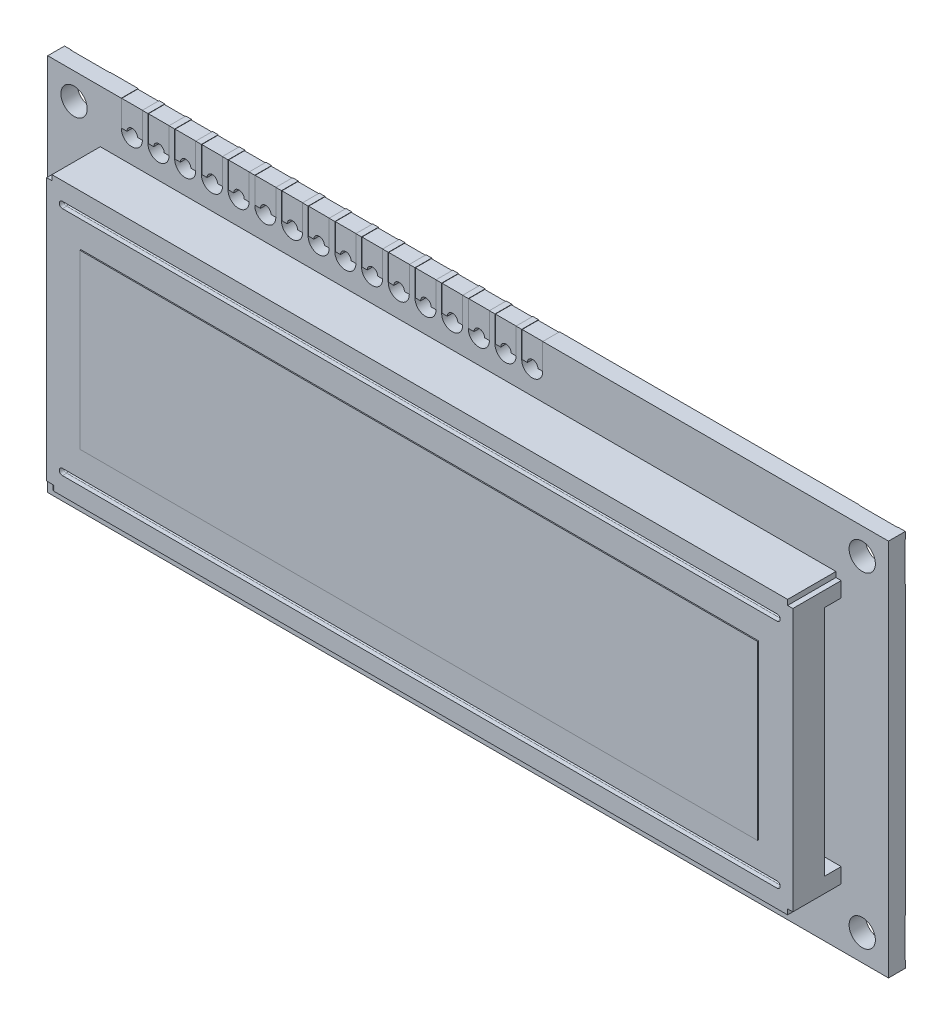
SolidWorks part; units mm, degrees
ref_plane "Front Plane" through (0, 0, 0) normal (0, 0, 1) x (1, 0, 0)
ref_plane "Top Plane" through (0, 0, 0) normal (0, 1, 0) x (1, 0, 0)
ref_plane "Right Plane" through (0, 0, 0) normal (1, 0, 0) x (0, 0, -1)
ref_plane "Plane1" through (0, 0, 6.2) normal (0, 0, 1) x (1, 0, 0)
sketch "Sketch1" plane through (0, 0, 6.2) normal (0, 0, 1) x (1, 0, 0)
  line L0 (-35, 13) -> (-35, -13)
  line L1 (-35, -13) -> (35, -13)
  line L2 (35, -13) -> (35, 13)
  line L3 (35, 13) -> (-35, 13)
extrude "Boss-Extrude1" add sketch "Sketch1" against normal blind 4.6
sketch "Sketch2" plane through (-35, 0, 0) normal (-1, 0, 0) x (0, 0, 1)
  line L0 (1.6, -12.5) -> (1.6, 12.5)
  line L1 (1.6, 12.5) -> (6.2, 12.5)
  line L2 (6.2, 12.5) -> (6.2, -12.5)
  line L3 (6.2, -12.5) -> (1.6, -12.5)
extrude "Boss-Extrude2" add sketch "Sketch2" along normal blind 0.5
sketch "Sketch3" plane through (35, 0, 0) normal (1, 0, 0) x (0, 0, -1)
  line L0 (-1.6, 12.5) -> (-1.6, -12.5)
  line L1 (-1.6, -12.5) -> (-6.2, -12.5)
  line L2 (-6.2, -12.5) -> (-6.2, 12.5)
  line L3 (-6.2, 12.5) -> (-1.6, 12.5)
extrude "Boss-Extrude3" add sketch "Sketch3" along normal blind 0.5
ref_plane "Plane2" through (0, 11.0678, 0) normal (0, 1, 0) x (1, 0, 0)
sketch "Sketch4" plane through (0, 11.0678, 0) normal (0, 1, 0) x (1, 0, 0)
  line L0 (-35.5, -3.2) -> (35.5, -3.2)
  line L1 (35.5, -3.2) -> (35.5, -1.6)
  line L2 (35.5, -1.6) -> (-35.5, -1.6)
  line L3 (-35.5, -1.6) -> (-35.5, -3.2)
extrude "Cut-Extrude1" cut sketch "Sketch4" against normal blind 22.1357
ref_plane "Plane3" through (0, 0, 1.6) normal (0, 0, 1) x (1, 0, 0)
sketch "Sketch5" plane through (0, 0, 1.6) normal (0, 0, 1) x (1, 0, 0)
  line L0 (-40, 18) -> (-40, -18)
  line L1 (-40, -18) -> (40, -18)
  line L2 (40, -18) -> (40, 18)
  line L3 (40, 18) -> (-40, 18)
extrude "Boss-Extrude4" add sketch "Sketch5" against normal blind 1.6
sketch "Sketch6" plane through (0, 0, 1.6) normal (0, 0, 1) x (1, 0, 0)
  line L0 (-31, 18) -> (-33, 18)
  line L1 (-33, 18) -> (-33, 15.5)
  line L2 (-31, 15.5) -> (-31, 18)
  arc A0 (-33, 15.5) -> (-31, 15.5) centre (-32, 15.5) ccw
extrude "Cut-Extrude2" cut sketch "Sketch6" against normal through all
sketch "Sketch7" plane through (0, 0, 1.6) normal (0, 0, 1) x (1, 0, 0)
  line L0 (-28.46, 18) -> (-30.46, 18)
  line L1 (-30.46, 18) -> (-30.46, 15.5)
  line L2 (-28.46, 15.5) -> (-28.46, 18)
  arc A0 (-30.46, 15.5) -> (-28.46, 15.5) centre (-29.46, 15.5) ccw
extrude "Cut-Extrude3" cut sketch "Sketch7" against normal through all
sketch "Sketch8" plane through (0, 0, 1.6) normal (0, 0, 1) x (1, 0, 0)
  line L0 (-25.92, 18) -> (-27.92, 18)
  line L1 (-27.92, 18) -> (-27.92, 15.5)
  line L2 (-25.92, 15.5) -> (-25.92, 18)
  arc A0 (-27.92, 15.5) -> (-25.92, 15.5) centre (-26.92, 15.5) ccw
extrude "Cut-Extrude4" cut sketch "Sketch8" against normal through all
sketch "Sketch9" plane through (0, 0, 1.6) normal (0, 0, 1) x (1, 0, 0)
  line L0 (-23.38, 18) -> (-25.38, 18)
  line L1 (-25.38, 18) -> (-25.38, 15.5)
  line L2 (-23.38, 15.5) -> (-23.38, 18)
  arc A0 (-25.38, 15.5) -> (-23.38, 15.5) centre (-24.38, 15.5) ccw
extrude "Cut-Extrude5" cut sketch "Sketch9" against normal through all
sketch "Sketch10" plane through (0, 0, 1.6) normal (0, 0, 1) x (1, 0, 0)
  line L0 (-20.84, 18) -> (-22.84, 18)
  line L1 (-22.84, 18) -> (-22.84, 15.5)
  line L2 (-20.84, 15.5) -> (-20.84, 18)
  arc A0 (-22.84, 15.5) -> (-20.84, 15.5) centre (-21.84, 15.5) ccw
extrude "Cut-Extrude6" cut sketch "Sketch10" against normal through all
sketch "Sketch11" plane through (0, 0, 1.6) normal (0, 0, 1) x (1, 0, 0)
  line L0 (-18.3, 18) -> (-20.3, 18)
  line L1 (-20.3, 18) -> (-20.3, 15.5)
  line L2 (-18.3, 15.5) -> (-18.3, 18)
  arc A0 (-20.3, 15.5) -> (-18.3, 15.5) centre (-19.3, 15.5) ccw
extrude "Cut-Extrude7" cut sketch "Sketch11" against normal through all
sketch "Sketch12" plane through (0, 0, 1.6) normal (0, 0, 1) x (1, 0, 0)
  line L0 (-15.76, 18) -> (-17.76, 18)
  line L1 (-17.76, 18) -> (-17.76, 15.5)
  line L2 (-15.76, 15.5) -> (-15.76, 18)
  arc A0 (-17.76, 15.5) -> (-15.76, 15.5) centre (-16.76, 15.5) ccw
extrude "Cut-Extrude8" cut sketch "Sketch12" against normal through all
sketch "Sketch13" plane through (0, 0, 1.6) normal (0, 0, 1) x (1, 0, 0)
  line L0 (-13.22, 18) -> (-15.22, 18)
  line L1 (-15.22, 18) -> (-15.22, 15.5)
  line L2 (-13.22, 15.5) -> (-13.22, 18)
  arc A0 (-15.22, 15.5) -> (-13.22, 15.5) centre (-14.22, 15.5) ccw
extrude "Cut-Extrude9" cut sketch "Sketch13" against normal through all
sketch "Sketch14" plane through (0, 0, 1.6) normal (0, 0, 1) x (1, 0, 0)
  line L0 (-10.68, 18) -> (-12.68, 18)
  line L1 (-12.68, 18) -> (-12.68, 15.5)
  line L2 (-10.68, 15.5) -> (-10.68, 18)
  arc A0 (-12.68, 15.5) -> (-10.68, 15.5) centre (-11.68, 15.5) ccw
extrude "Cut-Extrude10" cut sketch "Sketch14" against normal through all
sketch "Sketch15" plane through (0, 0, 1.6) normal (0, 0, 1) x (1, 0, 0)
  line L0 (-8.14, 18) -> (-10.14, 18)
  line L1 (-10.14, 18) -> (-10.14, 15.5)
  line L2 (-8.14, 15.5) -> (-8.14, 18)
  arc A0 (-10.14, 15.5) -> (-8.14, 15.5) centre (-9.14, 15.5) ccw
extrude "Cut-Extrude11" cut sketch "Sketch15" against normal through all
sketch "Sketch16" plane through (0, 0, 1.6) normal (0, 0, 1) x (1, 0, 0)
  line L0 (-5.6, 18) -> (-7.6, 18)
  line L1 (-7.6, 18) -> (-7.6, 15.5)
  line L2 (-5.6, 15.5) -> (-5.6, 18)
  arc A0 (-7.6, 15.5) -> (-5.6, 15.5) centre (-6.6, 15.5) ccw
extrude "Cut-Extrude12" cut sketch "Sketch16" against normal through all
sketch "Sketch17" plane through (0, 0, 1.6) normal (0, 0, 1) x (1, 0, 0)
  line L0 (-3.06, 18) -> (-5.06, 18)
  line L1 (-5.06, 18) -> (-5.06, 15.5)
  line L2 (-3.06, 15.5) -> (-3.06, 18)
  arc A0 (-5.06, 15.5) -> (-3.06, 15.5) centre (-4.06, 15.5) ccw
extrude "Cut-Extrude13" cut sketch "Sketch17" against normal through all
sketch "Sketch18" plane through (0, 0, 1.6) normal (0, 0, 1) x (1, 0, 0)
  line L0 (-0.52, 18) -> (-2.52, 18)
  line L1 (-2.52, 18) -> (-2.52, 15.5)
  line L2 (-0.52, 15.5) -> (-0.52, 18)
  arc A0 (-2.52, 15.5) -> (-0.52, 15.5) centre (-1.52, 15.5) ccw
extrude "Cut-Extrude14" cut sketch "Sketch18" against normal through all
sketch "Sketch19" plane through (0, 0, 1.6) normal (0, 0, 1) x (1, 0, 0)
  line L0 (2.02, 18) -> (0.02, 18)
  line L1 (0.02, 18) -> (0.02, 15.5)
  line L2 (2.02, 15.5) -> (2.02, 18)
  arc A0 (0.02, 15.5) -> (2.02, 15.5) centre (1.02, 15.5) ccw
extrude "Cut-Extrude15" cut sketch "Sketch19" against normal through all
sketch "Sketch20" plane through (0, 0, 1.6) normal (0, 0, 1) x (1, 0, 0)
  line L0 (5.1, 18) -> (5.1, 15.5)
  line L1 (7.1, 15.5) -> (7.1, 18)
  line L2 (7.1, 18) -> (5.1, 18)
  arc A0 (5.1, 15.5) -> (7.1, 15.5) centre (6.1, 15.5) ccw
extrude "Cut-Extrude16" cut sketch "Sketch20" against normal through all
sketch "Sketch21" plane through (-31, 0, 0) normal (-1, 0, 0) x (0, 0, 1)
  line L0 (1.56, 15.5) -> (0.04, 15.5)
  line L1 (0.04, 15.5) -> (0.04, 17.97)
  line L2 (0.04, 17.97) -> (1.56, 17.97)
  line L3 (1.56, 17.97) -> (1.56, 15.5)
extrude "Boss-Extrude5" add sketch "Sketch21" along normal blind 2
sketch "Sketch22" plane through (-28.46, 0, 0) normal (-1, 0, 0) x (0, 0, 1)
  line L0 (1.56, 15.5) -> (0.04, 15.5)
  line L1 (0.04, 15.5) -> (0.04, 17.97)
  line L2 (0.04, 17.97) -> (1.56, 17.97)
  line L3 (1.56, 17.97) -> (1.56, 15.5)
extrude "Boss-Extrude6" add sketch "Sketch22" along normal blind 2
sketch "Sketch23" plane through (-25.92, 0, 0) normal (-1, 0, 0) x (0, 0, 1)
  line L0 (1.56, 15.5) -> (0.04, 15.5)
  line L1 (0.04, 15.5) -> (0.04, 17.97)
  line L2 (0.04, 17.97) -> (1.56, 17.97)
  line L3 (1.56, 17.97) -> (1.56, 15.5)
extrude "Boss-Extrude7" add sketch "Sketch23" along normal blind 2
sketch "Sketch24" plane through (-23.38, 0, 0) normal (-1, 0, 0) x (0, 0, 1)
  line L0 (1.56, 15.5) -> (0.04, 15.5)
  line L1 (0.04, 15.5) -> (0.04, 17.97)
  line L2 (0.04, 17.97) -> (1.56, 17.97)
  line L3 (1.56, 17.97) -> (1.56, 15.5)
extrude "Boss-Extrude8" add sketch "Sketch24" along normal blind 2
sketch "Sketch25" plane through (-20.84, 0, 0) normal (-1, 0, 0) x (0, 0, 1)
  line L0 (1.56, 15.5) -> (0.04, 15.5)
  line L1 (0.04, 15.5) -> (0.04, 17.97)
  line L2 (0.04, 17.97) -> (1.56, 17.97)
  line L3 (1.56, 17.97) -> (1.56, 15.5)
extrude "Boss-Extrude9" add sketch "Sketch25" along normal blind 2
sketch "Sketch26" plane through (-18.3, 0, 0) normal (-1, 0, 0) x (0, 0, 1)
  line L0 (1.56, 15.5) -> (0.04, 15.5)
  line L1 (0.04, 15.5) -> (0.04, 17.97)
  line L2 (0.04, 17.97) -> (1.56, 17.97)
  line L3 (1.56, 17.97) -> (1.56, 15.5)
extrude "Boss-Extrude10" add sketch "Sketch26" along normal blind 2
sketch "Sketch27" plane through (-15.76, 0, 0) normal (-1, 0, 0) x (0, 0, 1)
  line L0 (1.56, 15.5) -> (0.04, 15.5)
  line L1 (0.04, 15.5) -> (0.04, 17.97)
  line L2 (0.04, 17.97) -> (1.56, 17.97)
  line L3 (1.56, 17.97) -> (1.56, 15.5)
extrude "Boss-Extrude11" add sketch "Sketch27" along normal blind 2
sketch "Sketch28" plane through (-13.22, 0, 0) normal (-1, 0, 0) x (0, 0, 1)
  line L0 (1.56, 15.5) -> (0.04, 15.5)
  line L1 (0.04, 15.5) -> (0.04, 17.97)
  line L2 (0.04, 17.97) -> (1.56, 17.97)
  line L3 (1.56, 17.97) -> (1.56, 15.5)
extrude "Boss-Extrude12" add sketch "Sketch28" along normal blind 2
sketch "Sketch29" plane through (-10.68, 0, 0) normal (-1, 0, 0) x (0, 0, 1)
  line L0 (1.56, 15.5) -> (0.04, 15.5)
  line L1 (0.04, 15.5) -> (0.04, 17.97)
  line L2 (0.04, 17.97) -> (1.56, 17.97)
  line L3 (1.56, 17.97) -> (1.56, 15.5)
extrude "Boss-Extrude13" add sketch "Sketch29" along normal blind 2
sketch "Sketch30" plane through (-8.14, 0, 0) normal (-1, 0, 0) x (0, 0, 1)
  line L0 (1.56, 15.5) -> (0.04, 15.5)
  line L1 (0.04, 15.5) -> (0.04, 17.97)
  line L2 (0.04, 17.97) -> (1.56, 17.97)
  line L3 (1.56, 17.97) -> (1.56, 15.5)
extrude "Boss-Extrude14" add sketch "Sketch30" along normal blind 2
sketch "Sketch31" plane through (-5.6, 0, 0) normal (-1, 0, 0) x (0, 0, 1)
  line L0 (1.56, 15.5) -> (0.04, 15.5)
  line L1 (0.04, 15.5) -> (0.04, 17.97)
  line L2 (0.04, 17.97) -> (1.56, 17.97)
  line L3 (1.56, 17.97) -> (1.56, 15.5)
extrude "Boss-Extrude15" add sketch "Sketch31" along normal blind 2
sketch "Sketch32" plane through (-3.06, 0, 0) normal (-1, 0, 0) x (0, 0, 1)
  line L0 (1.56, 15.5) -> (0.04, 15.5)
  line L1 (0.04, 15.5) -> (0.04, 17.97)
  line L2 (0.04, 17.97) -> (1.56, 17.97)
  line L3 (1.56, 17.97) -> (1.56, 15.5)
extrude "Boss-Extrude16" add sketch "Sketch32" along normal blind 2
sketch "Sketch33" plane through (-0.52, 0, 0) normal (-1, 0, 0) x (0, 0, 1)
  line L0 (1.56, 15.5) -> (0.04, 15.5)
  line L1 (0.04, 15.5) -> (0.04, 17.97)
  line L2 (0.04, 17.97) -> (1.56, 17.97)
  line L3 (1.56, 17.97) -> (1.56, 15.5)
extrude "Boss-Extrude17" add sketch "Sketch33" along normal blind 2
sketch "Sketch34" plane through (2.02, 0, 0) normal (-1, 0, 0) x (0, 0, 1)
  line L0 (1.56, 15.5) -> (0.04, 15.5)
  line L1 (0.04, 15.5) -> (0.04, 17.97)
  line L2 (0.04, 17.97) -> (1.56, 17.97)
  line L3 (1.56, 17.97) -> (1.56, 15.5)
extrude "Boss-Extrude18" add sketch "Sketch34" along normal blind 2
sketch "Sketch35" plane through (7.1, 0, 0) normal (-1, 0, 0) x (0, 0, 1)
  line L0 (1.56, 15.5) -> (0.04, 15.5)
  line L1 (0.04, 15.5) -> (0.04, 17.97)
  line L2 (0.04, 17.97) -> (1.56, 17.97)
  line L3 (1.56, 17.97) -> (1.56, 15.5)
extrude "Boss-Extrude19" add sketch "Sketch35" along normal blind 2
sketch "Sketch36" plane through (0, 0, 1.6) normal (0, 0, 1) x (1, 0, 0)
  line L0 (4.56, 18) -> (2.56, 18)
  line L1 (2.56, 18) -> (2.56, 15.5)
  line L2 (4.56, 15.5) -> (4.56, 18)
  arc A0 (2.56, 15.5) -> (4.56, 15.5) centre (3.56, 15.5) ccw
extrude "Cut-Extrude17" cut sketch "Sketch36" against normal through all
sketch "Sketch37" plane through (4.56, 0, 0) normal (-1, 0, 0) x (0, 0, 1)
  line L0 (1.56, 15.5) -> (0.04, 15.5)
  line L1 (0.04, 15.5) -> (0.04, 17.97)
  line L2 (0.04, 17.97) -> (1.56, 17.97)
  line L3 (1.56, 17.97) -> (1.56, 15.5)
extrude "Boss-Extrude20" add sketch "Sketch37" along normal blind 2
sketch "Sketch38" plane through (0, 0, 6.2) normal (0, 0, 1) x (1, 0, 0)
  line L0 (32.25, 8.2) -> (32.25, -8.2)
  line L1 (32.25, -8.2) -> (-32.25, -8.2)
  line L2 (-32.25, -8.2) -> (-32.25, 8.2)
  line L3 (-32.25, 8.2) -> (32.25, 8.2)
extrude "Boss-Extrude21" add sketch "Sketch38" along normal blind 0.1
sketch "Sketch39" plane through (0, 0, 0) normal (0, 0, -1) x (-1, 0, 0)
  line L0 (-30.7, 0.5) -> (-29.9, 0.5)
  line L1 (-29.9, 0.5) -> (-29.9, 0)
  line L2 (-29.9, 0) -> (-30.7, 0)
  line L3 (-30.7, 0) -> (-30.7, 0.5)
extrude "Boss-Extrude22" add sketch "Sketch39" along normal blind 0.6
sketch "Sketch40" plane through (0, 0, 0) normal (0, 0, -1) x (-1, 0, 0)
  line L0 (-32, 0.5) -> (-31.2, 0.5)
  line L1 (-31.2, 0.5) -> (-31.2, 0)
  line L2 (-31.2, 0) -> (-32, 0)
  line L3 (-32, 0) -> (-32, 0.5)
extrude "Boss-Extrude23" add sketch "Sketch40" along normal blind 0.6
sketch "Sketch41" plane through (0, 0, 0) normal (0, 0, -1) x (-1, 0, 0)
  line L0 (-30.7, -1.5) -> (-29.9, -1.5)
  line L1 (-29.9, -1.5) -> (-29.9, -2)
  line L2 (-29.9, -2) -> (-30.7, -2)
  line L3 (-30.7, -2) -> (-30.7, -1.5)
extrude "Boss-Extrude24" add sketch "Sketch41" along normal blind 0.6
sketch "Sketch42" plane through (0, 0, 0) normal (0, 0, -1) x (-1, 0, 0)
  line L0 (-32, -1.5) -> (-31.2, -1.5)
  line L1 (-31.2, -1.5) -> (-31.2, -2)
  line L2 (-31.2, -2) -> (-32, -2)
  line L3 (-32, -2) -> (-32, -1.5)
extrude "Boss-Extrude25" add sketch "Sketch42" along normal blind 0.6
sketch "Sketch43" plane through (0, 0, 0) normal (0, 0, -1) x (-1, 0, 0)
  line L0 (-30.7, -2.5) -> (-29.9, -2.5)
  line L1 (-29.9, -2.5) -> (-29.9, -3)
  line L2 (-29.9, -3) -> (-30.7, -3)
  line L3 (-30.7, -3) -> (-30.7, -2.5)
extrude "Boss-Extrude26" add sketch "Sketch43" along normal blind 0.6
sketch "Sketch44" plane through (0, 0, 0) normal (0, 0, -1) x (-1, 0, 0)
  line L0 (-32, -2.5) -> (-31.2, -2.5)
  line L1 (-31.2, -2.5) -> (-31.2, -3)
  line L2 (-31.2, -3) -> (-32, -3)
  line L3 (-32, -3) -> (-32, -2.5)
extrude "Boss-Extrude27" add sketch "Sketch44" along normal blind 0.6
sketch "Sketch45" plane through (0, 0, 0) normal (0, 0, -1) x (-1, 0, 0)
  line L0 (-30.7, -3.5) -> (-29.9, -3.5)
  line L1 (-29.9, -3.5) -> (-29.9, -4)
  line L2 (-29.9, -4) -> (-30.7, -4)
  line L3 (-30.7, -4) -> (-30.7, -3.5)
extrude "Boss-Extrude28" add sketch "Sketch45" along normal blind 0.6
sketch "Sketch46" plane through (0, 0, 0) normal (0, 0, -1) x (-1, 0, 0)
  line L0 (-32, -3.5) -> (-31.2, -3.5)
  line L1 (-31.2, -3.5) -> (-31.2, -4)
  line L2 (-31.2, -4) -> (-32, -4)
  line L3 (-32, -4) -> (-32, -3.5)
extrude "Boss-Extrude29" add sketch "Sketch46" along normal blind 0.6
sketch "Sketch47" plane through (0, 0, 0) normal (0, 0, -1) x (-1, 0, 0)
  line L0 (-30.7, -4.5) -> (-29.9, -4.5)
  line L1 (-29.9, -4.5) -> (-29.9, -5)
  line L2 (-29.9, -5) -> (-30.7, -5)
  line L3 (-30.7, -5) -> (-30.7, -4.5)
extrude "Boss-Extrude30" add sketch "Sketch47" along normal blind 0.6
sketch "Sketch48" plane through (0, 0, 0) normal (0, 0, -1) x (-1, 0, 0)
  line L0 (-32, -4.5) -> (-31.2, -4.5)
  line L1 (-31.2, -4.5) -> (-31.2, -5)
  line L2 (-31.2, -5) -> (-32, -5)
  line L3 (-32, -5) -> (-32, -4.5)
extrude "Boss-Extrude31" add sketch "Sketch48" along normal blind 0.6
sketch "Sketch49" plane through (0, 0, 0) normal (0, 0, -1) x (-1, 0, 0)
  line L0 (-32, -0.5) -> (-31.2, -0.5)
  line L1 (-31.2, -0.5) -> (-31.2, -1)
  line L2 (-31.2, -1) -> (-32, -1)
  line L3 (-32, -1) -> (-32, -0.5)
extrude "Boss-Extrude32" add sketch "Sketch49" along normal blind 0.6
sketch "Sketch50" plane through (0, 0, 0) normal (0, 0, -1) x (-1, 0, 0)
  line L0 (-30.7, -0.5) -> (-29.9, -0.5)
  line L1 (-29.9, -0.5) -> (-29.9, -1)
  line L2 (-29.9, -1) -> (-30.7, -1)
  line L3 (-30.7, -1) -> (-30.7, -0.5)
extrude "Boss-Extrude33" add sketch "Sketch50" along normal blind 0.6
sketch "Sketch51" plane through (0, 0, 6.2) normal (0, 0, 1) x (1, 0, 0)
  line L0 (34, -10.7) -> (-34, -10.7)
  line L1 (-34, -11.3) -> (34, -11.3)
  arc A0 (-34, -10.7) -> (-34, -11.3) centre (-34, -11) ccw
  arc A1 (34, -11.3) -> (34, -10.7) centre (34, -11) ccw
extrude "Cut-Extrude18" cut sketch "Sketch51" against normal blind 0.5
sketch "Sketch52" plane through (0, 0, 6.2) normal (0, 0, 1) x (1, 0, 0)
  line L0 (34, 11.3) -> (-34, 11.3)
  line L1 (-34, 10.7) -> (34, 10.7)
  arc A0 (34, 10.7) -> (34, 11.3) centre (34, 11) ccw
  arc A1 (-34, 11.3) -> (-34, 10.7) centre (-34, 11) ccw
extrude "Cut-Extrude19" cut sketch "Sketch52" against normal blind 0.5
ref_plane "Plane4" through (0, 0, 0) normal (0, -1, 0) x (1, 0, 0)
sketch "Sketch53" plane through (0, 0, 0) normal (0, -1, 0) x (1, 0, 0)
  line L0 (-9.6621, 0) -> (-14.0187, 0)
  line L1 (-14.0187, 0) -> (-14.0187, -1)
  line L2 (-14.0187, -1) -> (-11.3942, -1)
  line L3 (-14.0187, 0) -> (-14.0187, -1) construction
  arc A0 (-11.3942, -1) -> (-10.5281, -0.5) centre (-11.3942, 0) ccw
  arc A1 (-10.5281, -0.5) -> (-9.6621, 0) centre (-9.6621, -1) cw
revolve "Revolve1" add sketch "Sketch53" angle 360 about L3 reverse direction yes
sketch "Sketch54" plane through (0, 0, 0) normal (0, -1, 0) x (1, 0, 0)
  line L0 (23.145, 0) -> (17.1975, 0)
  line L1 (17.1975, 0) -> (17.1975, -1)
  line L2 (17.1975, -1) -> (21.413, -1)
  line L3 (17.1975, 0) -> (17.1975, -1) construction
  arc A0 (21.413, -1) -> (22.279, -0.5) centre (21.413, 0) ccw
  arc A1 (22.279, -0.5) -> (23.145, 0) centre (23.145, -1) cw
revolve "Revolve2" add sketch "Sketch54" angle 360 about L3 reverse direction yes
hole_wizard "M2.5x0.45 Tapped Hole1" positions "Sketch56" profile "Sketch55" tap size "M2.5x0.45" standard "ANSI Metric"
sketch "Sketch56" plane through (0, 0, 1.6) normal (0, 0, 1) x (1, 0, 0)
  point P0 (-37.5, -15.5)
  point P1 (37.5, -15.5)
  point P2 (-37.5, 15.5)
  point P3 (37.5, 15.5)
sketch "Sketch55" plane through (-37.5, -15.5, 1.6) normal (1, 0, 0) x (0, -1, 0)
  line L0 (0, 0) -> (0, 2.6)
  line L1 (0, 2.6) -> (3.1, 2.6)
  line L3 (3.1, 2.6) -> (3.1, 1.56)
  line L4 (3.1, 1.56) -> (1.25, 1.56)
  line L5 (1.25, 1.56) -> (1.25, 0)
  line L7 (1.25, 0) -> (0, 0)
  line L11 (0, -6.35) -> (0, 107.95) construction
  dimension "Thru Tap Drill Dia." = 6.2
  dimension "Thru Tap Drill Depth" = 2.6
  dimension "Thread Major Dia." = 2.5
  dimension "Thread Depth" = 1.56
hole_wizard "Ø1.0 (1) Diameter Hole1" positions "Sketch58" profile "Sketch57" hole size "Ø1.0" standard "ANSI Metric"
sketch "Sketch58" plane through (0, 0, 1.56) normal (0, 0, 1) x (1, 0, 0)
  point P0 (6.1, 15.5)
  point P1 (-32, 15.5)
  point P2 (-29.46, 15.5)
  point P3 (-26.92, 15.5)
  point P4 (-24.38, 15.5)
  point P5 (-21.84, 15.5)
  point P6 (-19.3, 15.5)
  point P7 (-16.76, 15.5)
  point P8 (-14.22, 15.5)
  point P9 (-11.68, 15.5)
  point P10 (-9.14, 15.5)
  point P11 (-6.6, 15.5)
  point P12 (-4.06, 15.5)
  point P13 (-1.52, 15.5)
  point P14 (1.02, 15.5)
  point P15 (3.56, 15.5)
sketch "Sketch57" plane through (6.1, 15.5, 1.56) normal (1, 0, 0) x (0, -1, 0)
  line L0 (0, 0) -> (0, 2.56)
  line L1 (0, 2.56) -> (0.5, 2.56)
  line L2 (0.5, 2.56) -> (0.5, 0)
  line L5 (0.5, 0) -> (0, 0)
  line L11 (0, -6.35) -> (0, 107.95) construction
  dimension "Thru Hole Dia." = 1
  dimension "Thru Hole Depth" = 2.56
ref_plane "Plane5" through (0, -4.75, 0) normal (0, 1, 0) x (1, 0, 0)
sketch "Sketch59" plane through (0, -4.75, 0) normal (0, 1, 0) x (1, 0, 0)
  line L0 (31.2, 0.5) -> (30.7, 0.5)
rib "Rib1" sketch "Sketch59" sketch "Sketch59" thickness 0.2 extrusion direction parallel to sketch draft on no parameters "D1"=0.2
ref_plane "Plane6" through (0, -1.75, 0) normal (0, 1, 0) x (1, 0, 0)
sketch "Sketch60" plane through (0, -1.75, 0) normal (0, 1, 0) x (1, 0, 0)
  line L0 (31.2, 0.5) -> (30.7, 0.5)
rib "Rib2" sketch "Sketch60" sketch "Sketch60" thickness 0.2 extrusion direction parallel to sketch draft on no parameters "D1"=0.2
ref_plane "Plane7" through (0, -3.75, 0) normal (0, 1, 0) x (1, 0, 0)
sketch "Sketch61" plane through (0, -3.75, 0) normal (0, 1, 0) x (1, 0, 0)
  line L0 (31.2, 0.5) -> (30.7, 0.5)
rib "Rib3" sketch "Sketch61" sketch "Sketch61" thickness 0.2 extrusion direction parallel to sketch draft on no parameters "D1"=0.2
ref_plane "Plane8" through (0, -0.75, 0) normal (0, 1, 0) x (1, 0, 0)
sketch "Sketch62" plane through (0, -0.75, 0) normal (0, 1, 0) x (1, 0, 0)
  line L0 (31.2, 0.5) -> (30.7, 0.5)
rib "Rib4" sketch "Sketch62" sketch "Sketch62" thickness 0.2 extrusion direction parallel to sketch draft on no parameters "D1"=0.2
ref_plane "Plane9" through (0, -2.75, 0) normal (0, 1, 0) x (1, 0, 0)
sketch "Sketch63" plane through (0, -2.75, 0) normal (0, 1, 0) x (1, 0, 0)
  line L0 (31.2, 0.5) -> (30.7, 0.5)
rib "Rib5" sketch "Sketch63" sketch "Sketch63" thickness 0.2 extrusion direction parallel to sketch draft on no parameters "D1"=0.2
ref_plane "Plane10" through (0, 0.25, 0) normal (0, 1, 0) x (1, 0, 0)
sketch "Sketch64" plane through (0, 0.25, 0) normal (0, 1, 0) x (1, 0, 0)
  line L0 (31.2, 0.5) -> (30.7, 0.5)
rib "Rib6" sketch "Sketch64" sketch "Sketch64" thickness 0.2 extrusion direction parallel to sketch draft on no parameters "D1"=0.2
fillet "Fillet2" radius 0.2 1 edges at (-35, -12.75, 6.2) tangent propagation no
chamfer "Chamfer1" distance 0.05 angle 45 12 edges at (30.95, -2.65, -0.5) (30.95, -4.65, -0.5) (30.95, -0.85, -0.5) (30.95, -3.65, -0.5) (30.95, -1.85, -0.5) (30.95, -3.85, -0.5) (30.95, -1.65, -0.5) (30.95, -4.85, -0.5) (30.95, -2.85, -0.5) (30.95, 0.35, -0.5) (30.95, -0.65, -0.5) (30.95, 0.15, -0.5)
fillet "Fillet3" radius 0.1 8 edges at (34.3, -11, 5.7) (0, -11.3, 5.7) (0, -10.7, 5.7) (-34.3, -11, 5.7) (0, 10.7, 5.7) (-34.3, 11, 5.7) (34.3, 11, 5.7) (0, 11.3, 5.7) tangent propagation no
